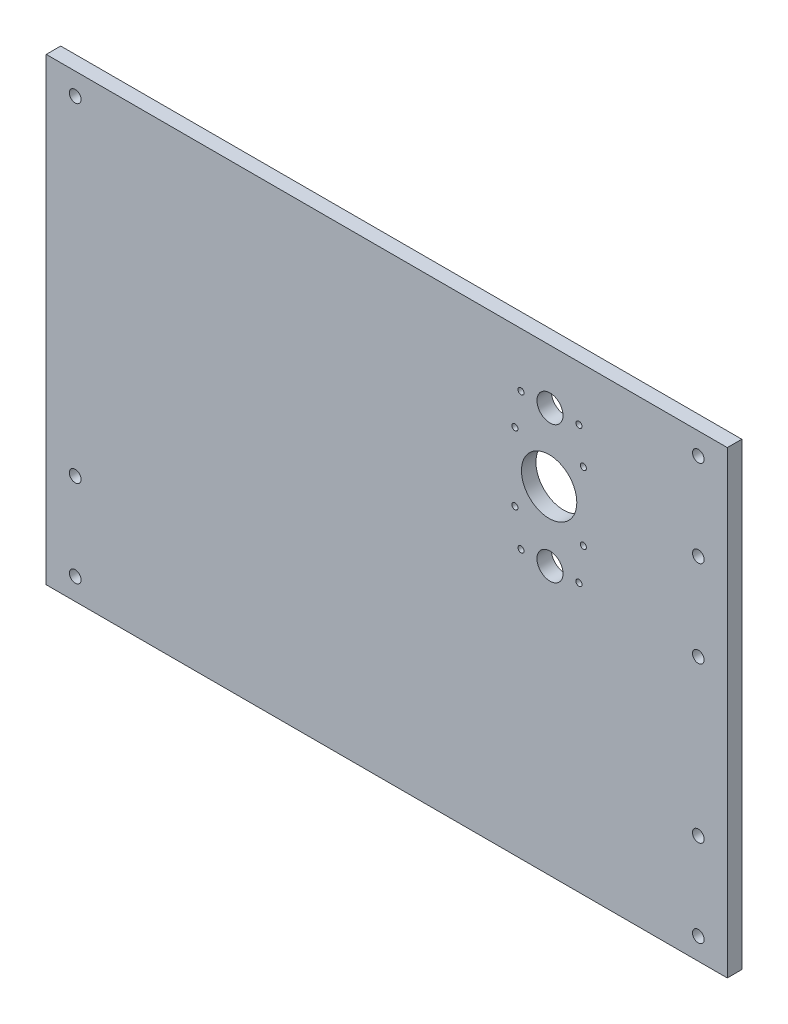
SolidWorks part; units mm, degrees
material "6061 Alloy"
ref_plane "Front Plane" through (0, 0, 0) normal (0, 0, 1) x (1, 0, 0)
ref_plane "Top Plane" through (0, 0, 0) normal (0, 1, 0) x (1, 0, 0)
ref_plane "Right Plane" through (0, 0, 0) normal (1, 0, 0) x (0, 0, -1)
sketch "Sketch2" plane through (0, 0, 0) normal (0, 0, 1) x (1, 0, 0)
  line L1 (-235, -158.5) -> (235, -158.5)
  line L2 (-235, -158.5) -> (-235, 158.5)
  line L3 (-235, 158.5) -> (235, 158.5)
  line L4 (235, -158.5) -> (235, 158.5)
  line L5 (-235, -158.5) -> (235, 158.5) construction
  line L6 (-235, 158.5) -> (235, -158.5) construction
  point P0 (0, 0)
  dimension "D1" = 470
  dimension "D2" = 317
extrude "Boss-Extrude1" add sketch "Sketch2" along normal mid plane 10
sketch "Sketch3" plane through (0, 0, 5) normal (0, 0, 1) x (1, 0, 0)
  line L0 (-215, -1058.5557) -> (-215, 48941.4443) construction
  line L1 (-235, 158.5) -> (-235, -158.5) construction
  line L2 (-1130.8828, -143.5) -> (48869.1172, -143.5) construction
  line L3 (-1138.1256, -83.5) -> (48861.8744, -83.5) construction
  line L4 (-235, -158.5) -> (235, -158.5) construction
  line L5 (215, -1025.1068) -> (215, 48974.8932) construction
  line L6 (235, -158.5) -> (235, 158.5) construction
  line L7 (-1174.5815, 143.5) -> (48825.4185, 143.5) construction
  line L8 (235, 158.5) -> (-235, 158.5) construction
  circle A0 centre (-215, -83.5) radius 4.05
  circle A1 centre (-215, -143.5) radius 4.05
  circle A2 centre (215, -83.5) radius 4.05
  circle A3 centre (215, -143.5) radius 4.05
  circle A4 centre (-215, 143.5) radius 4.05
  dimension "D5" = 8.1
  dimension "D6" = 8.1
  dimension "D7" = 8.1
  dimension "D8" = 8.1
  dimension "D10" = 8.1
  dimension "D1" = 20
  dimension "D2" = 15
  dimension "D3" = 60
  dimension "D4" = 20
  dimension "D9" = 15
extrude "Cut-Extrude1" cut sketch "Sketch3" against normal blind 10
sketch "Sketch4" plane through (0, 0, 5) normal (0, 0, 1) x (1, 0, 0)
  line L0 (-1048.1305, 121) -> (48951.8695, 121) construction
  line L1 (-1078.5537, 26.5) -> (48921.4463, 26.5) construction
  line L2 (112.65, -948.1906) -> (112.65, 49051.8094) construction
  line L3 (-235, -158.5) -> (235, -158.5) construction
  line L4 (-235, 158.5) -> (-235, -158.5) construction
  circle A0 centre (112.65, 121) radius 9
  circle A1 centre (112.65, 26.5) radius 9
  circle A2 centre (92.65, 121) radius 2.1
  circle A3 centre (132.65, 121) radius 2.1
  circle A4 centre (132.65, 26.5) radius 2.1
  circle A5 centre (92.65, 26.5) radius 2.1
  dimension "D4" = 18
  dimension "D5" = 18
  dimension "D8" = 4.2
  dimension "D9" = 4.2
  dimension "D12" = 4.2
  dimension "D13" = 4.2
  dimension "D1" = 185
  dimension "D2" = 94.5
  dimension "D3" = 347.65
  dimension "D6" = 20
  dimension "D7" = 20
  dimension "D10" = 20
  dimension "D11" = 20
extrude "Cut-Extrude2" cut sketch "Sketch4" against normal through all
sketch "Sketch7" plane through (0, 0, 5) normal (0, 0, 1) x (1, 0, 0)
  circle A0 centre (112.05, 73.75) radius 19.1
  circle A1 centre (112.65, 121) radius 9 construction
  dimension "D1" = 38.2
  dimension "D2" = 0.6
  dimension "D3" = 47.25
extrude "Cut-Extrude5" cut sketch "Sketch7" against normal through all
sketch "Sketch9" plane through (0, 0, 5) normal (0, 0, 1) x (1, 0, 0)
  line L1 (88.45, 50.15) -> (135.65, 50.15) construction
  line L2 (88.45, 50.15) -> (88.45, 97.35) construction
  line L3 (88.45, 97.35) -> (135.65, 97.35) construction
  line L4 (135.65, 50.15) -> (135.65, 97.35) construction
  line L5 (88.45, 50.15) -> (135.65, 97.35) construction
  line L6 (88.45, 97.35) -> (135.65, 50.15) construction
  circle A0 centre (88.45, 97.35) radius 2.1
  circle A1 centre (135.65, 97.35) radius 2.1
  circle A2 centre (135.65, 50.15) radius 2.1
  circle A3 centre (88.45, 50.15) radius 2.1
  circle A7 centre (112.05, 73.75) radius 19.1 construction
  point P0 (112.05, 73.75)
  dimension "D3" = 4.2
  dimension "D4" = 4.2
  dimension "D5" = 4.2
  dimension "D6" = 4.2
  dimension "D1" = 47.2
  dimension "D2" = 47.2
extrude "Cut-Extrude7" cut sketch "Sketch9" against normal through all
sketch "Sketch10" plane through (0, 0, 5) normal (0, 0, 1) x (1, 0, 0)
  line L0 (235, 158.5) -> (-235, 158.5) construction
  line L1 (235, -158.5) -> (235, 158.5) construction
  circle A0 centre (215, 143.5) radius 4
  dimension "D1" = 15
  dimension "D3" = 8
  dimension "D2" = 20
extrude "Cut-Extrude8" cut sketch "Sketch10" against normal through all
pattern_linear "LPattern1" count 1 spacing 60 along (-1, 0, 0) count 3 spacing 60 along (0, -1, 0) of "Cut-Extrude8"
sketch "Sketch11" [suppressed] plane through (0, 0, 5) normal (0, 0, 1) x (1, 0, 0)
  line L0 (112.65, 121) -> (112.65, 26.5) construction
  circle A0 centre (112.65, 73.75) radius 5
  dimension "D1" = 10
extrude "Cut-Extrude9" [suppressed] cut sketch "Sketch11" against normal through all
sketch "Sketch12" [suppressed] plane through (0, 0, 5) normal (0, 0, 1) x (1, 0, 0)
  line L1 (101.65, 62.75) -> (123.65, 62.75) construction
  line L2 (101.65, 62.75) -> (101.65, 84.75) construction
  line L3 (101.65, 84.75) -> (123.65, 84.75) construction
  line L4 (123.65, 62.75) -> (123.65, 84.75) construction
  line L5 (101.65, 62.75) -> (123.65, 84.75) construction
  line L6 (101.65, 84.75) -> (123.65, 62.75) construction
  circle A0 centre (101.65, 84.75) radius 1.45
  circle A1 centre (123.65, 84.75) radius 1.45
  circle A2 centre (123.65, 62.75) radius 1.45
  circle A3 centre (101.65, 62.75) radius 1.45
  point P0 (112.65, 73.75)
  dimension "D3" = 2.9
  dimension "D4" = 2.9
  dimension "D5" = 2.9
  dimension "D6" = 2.9
  dimension "D1" = 22
  dimension "D2" = 22
extrude "Cut-Extrude10" [suppressed] cut sketch "Sketch12" against normal through all
equation "\"D6@Sketch3\"=\"D5@Sketch3\""
equation "\"D7@Sketch3\"=\"D5@Sketch3\""
equation "\"D8@Sketch3\"=\"D5@Sketch3\""
equation "\"D5@Sketch4\"=\"D4@Sketch4\""
equation "\"D4@Sketch9\" = \"D3@Sketch9\""
equation "\"D5@Sketch9\"=\"D3@Sketch9\""
equation "\"D6@Sketch9\"=\"D3@Sketch9\""
equation "\"D3@Sketch7\"=94.5/2"
equation "\"D10@Sketch3\"=\"D5@Sketch3\""
equation "\"D4@Sketch12\"=\"D3@Sketch12\""
equation "\"D5@Sketch12\"=\"D3@Sketch12\""
equation "\"D6@Sketch12\"=\"D3@Sketch12\""
